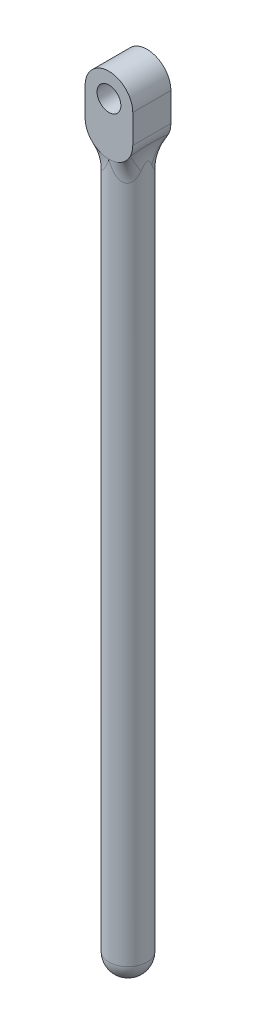
SolidWorks part; units mm, degrees
material "Thornel VCB-20 Carbon Cloth"
ref_plane "Front Plane" through (0, 0, 0) normal (0, 0, 1) x (1, 0, 0)
ref_plane "Top Plane" through (0, 0, 0) normal (0, 1, 0) x (1, 0, 0)
ref_plane "Right Plane" through (0, 0, 0) normal (1, 0, 0) x (0, 0, -1)
sketch "Sketch1" plane through (0, 0, 0) normal (0, 0, 1) x (1, 0, 0)
  line L0 (0, 0) -> (0, -6) construction
  line L1 (5, 0) -> (5, -6)
  line L2 (-5, 0) -> (-5, -6)
  arc A0 (5, 0) -> (-5, 0) centre (0, 0) ccw
  arc A1 (-5, -6) -> (5, -6) centre (0, -6) ccw
  circle A2 centre (0, 0) radius 2.5
  point P3 (0, -3)
  dimension "D3" = 5
  dimension "D1" = 6
  dimension "D2" = 10
extrude "Boss-Extrude1" add sketch "Sketch1" along normal blind 8
ref_plane "Plane1" through (0, -11, 0) normal (0, -1, 0) x (-1, 0, 0)
sketch "Sketch2" plane through (0, -11, 0) normal (0, -1, 0) x (-1, 0, 0)
  line L0 (0, -8) -> (0, 0) construction
  line L1 (-5, -8) -> (5, -8) construction
  circle A0 centre (0, -4) radius 4
  dimension "D1" = 8
extrude "Boss-Extrude2" add sketch "Sketch2" along normal blind 150 and the other way up to surface
fillet "Fillet1" radius 4 1 edges at (0, -161, 0)
fillet "Fillet2" radius 10 2 edges at (-3.9864, -9.0181, 4.3298) (3.9864, -9.0181, 3.6702)
